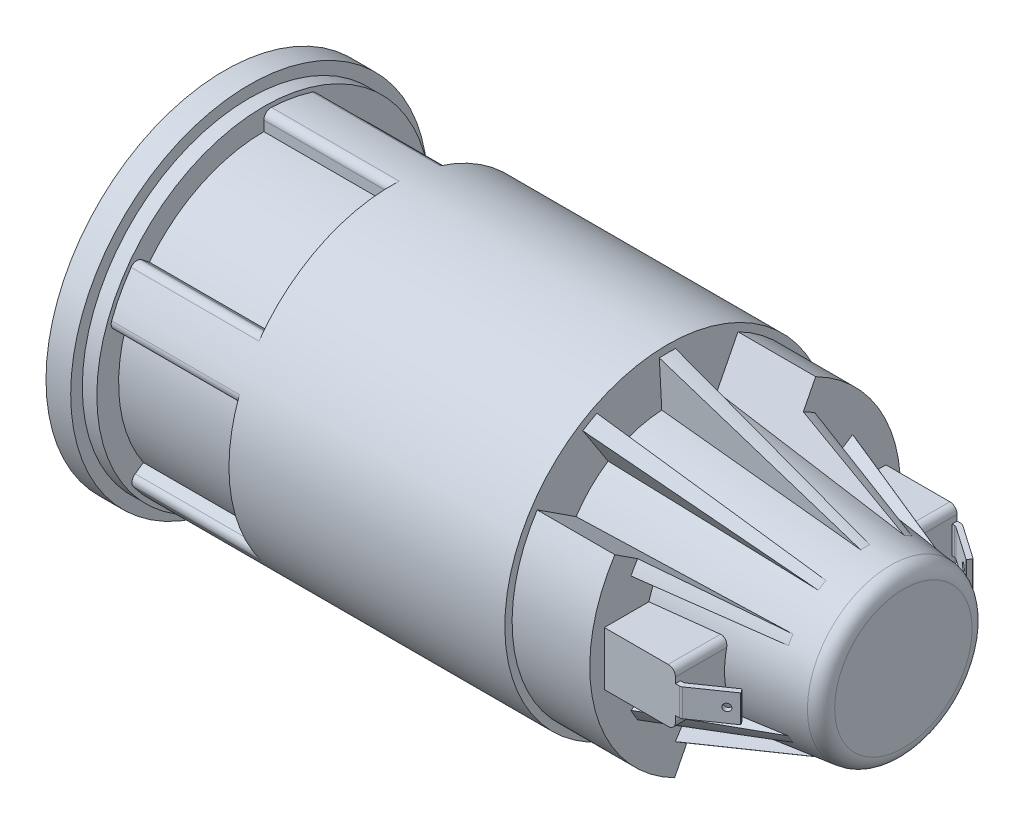
SolidWorks part; units mm, degrees
ref_plane "Front Plane" through (0, 0, 0) normal (0, 0, 1) x (1, 0, 0)
ref_plane "Top Plane" through (0, 0, 0) normal (0, 1, 0) x (1, 0, 0)
ref_plane "Right Plane" through (0, 0, 0) normal (1, 0, 0) x (0, 0, -1)
sketch "Sketch1" plane through (0, 0, 0) normal (1, 0, 0) x (0, 0, -1)
  circle A0 centre (0, 0) radius 7.493
  dimension "D1" = 14.986
extrude "Extrude1" add sketch "Sketch1" along normal blind 8.89
sketch "Sketch2" plane through (8.89, 0, 0) normal (1, 0, 0) x (0, 0, -1)
  circle A0 centre (0, 0) radius 31.242
  dimension "D1" = 62.484
extrude "Extrude2" add sketch "Sketch2" along normal blind 10.922
sketch "Sketch3" plane through (8.89, 0, 0) normal (-1, 0, 0) x (0, 0, 1)
  circle A0 centre (0, 0) radius 21.971
  circle A2 centre (0, 0) radius 7.493
  dimension "D1" = 43.942
extrude "Extrude3" cut sketch "Sketch3" against normal blind 5.969
sketch "Sketch4" plane through (8.89, 0, 0) normal (-1, 0, 0) x (0, 0, 1)
  circle A0 centre (0, 0) radius 23.8125
  circle A1 centre (0, 0) radius 31.242
  dimension "D1" = 47.625
extrude "Extrude4" cut sketch "Sketch4" against normal blind 4.064
sketch "Sketch5" plane through (14.859, 0, 0) normal (-1, 0, 0) x (0, 0, 1)
  circle A0 centre (0, 0) radius 9.144
  circle A1 centre (0, 0) radius 12.7
  dimension "D1" = 18.288
  dimension "D2" = 25.4
extrude "Extrude5" add sketch "Sketch5" along normal blind 3.048
sketch "Sketch6" plane through (19.812, 0, 0) normal (1, 0, 0) x (0, 0, -1)
  circle A0 centre (0, 0) radius 25.4
  dimension "D1" = 50.8
extrude "Extrude6" add sketch "Sketch6" along normal blind 22.352
sketch "Sketch7" plane through (19.812, 0, 0) normal (1, 0, 0) x (0, 0, -1)
  line L0 (0, 25.4) -> (0, 27.1483)
  line L1 (8.6873, 23.8682) -> (9.2853, 25.5111)
  circle A0 centre (0, 0) radius 31.242 construction
  arc A1 (8.47, 27.1578) -> (1.3293, 28.4169) centre (0, 0) ccw
  arc A2 (8.6873, 23.8682) -> (0, 25.4) centre (0, 0) ccw
  arc A3 (1.3293, 28.4169) -> (0, 27.1483) centre (1.27, 27.1483) ccw
  arc A4 (8.47, 27.1578) -> (9.2853, 25.5111) centre (8.0919, 25.9454) cw
  point P11 (0, 31.242)
  point P14 (10.6854, 29.3579)
  dimension "D2" = 1.27
  dimension "D1" = 56.896
extrude "Extrude7" add sketch "Sketch7" along normal up to surface (22.352 mm away) up to face at (42.164, 0, -25.4)
ref_axis "Axis1" through (-3.3782, 0, 0) along (1, 0, 0)
pattern_circular "CirPattern1" count 5 over 360 about axis through (-3.3782, 0, 0) along (1, 0, 0) of "Extrude7"
sketch "Sketch8" plane through (42.164, 0, 0) normal (1, 0, 0) x (0, 0, -1)
  circle A0 centre (0, 0) radius 28.448
  dimension "D1" = 56.896
extrude "Extrude8" add sketch "Sketch8" along normal blind 48.26
sketch "Sketch9" plane through (0, 0, 0) normal (0, 0, 1) x (1, 0, 0)
  line L0 (90.424, -28.448) -> (90.424, 28.448) construction
  line L1 (90.424, 0) -> (90.424, 19.05)
  line L2 (90.424, 0) -> (131.699, 0)
  line L3 (131.699, 0) -> (131.699, 12.0237)
  line L4 (129.4501, 14.547) -> (90.424, 19.05)
  arc A0 (129.4501, 14.547) -> (131.699, 12.0237) centre (129.159, 12.0237) cw
  point P9 (131.699, 14.2875)
  dimension "D4" = 2.54
  dimension "D1" = 14.2875
  dimension "D2" = 19.05
  dimension "D3" = 41.275
revolve "Revolve1" add sketch "Sketch9" angle 360 about axis through (-3.3782, 0, 0) along (1, 0, 0)
sketch "Sketch10" plane through (0, 0, 0) normal (0, 0, 1) x (1, 0, 0)
  line L0 (129.4501, 14.547) -> (90.424, 19.05) construction
  line L1 (125.0051, 15.0599) -> (90.424, 19.05)
  line L2 (90.424, -28.448) -> (90.424, 28.448) construction
  line L3 (90.424, 19.05) -> (90.424, 27.178)
  line L4 (125.0051, 15.0599) -> (90.424, 27.178)
  dimension "D1" = 4.445
  dimension "D2" = 1.27
revolve "Revolve2" add sketch "Sketch10" angle 6 mid plane about axis through (-3.3782, 0, 0) along (1, 0, 0)
pattern_circular "CirPattern2" count 12 over 360 of "Revolve2"
sketch "Sketch11" plane through (90.424, 0, 0) normal (1, 0, 0) x (0, 0, -1)
  line L0 (22.7934, -14.8022) -> (15.9767, -10.3754) construction
  line L1 (22.7934, -14.8022) -> (15.9767, -10.3754)
  line L2 (12.3386, 24.2158) -> (8.6485, 16.9737) construction
  line L3 (12.3386, 24.2158) -> (8.6485, 16.9737)
  line L4 (8.6485, 16.9737) -> (6.837, 13.4184)
  line L5 (15.9767, -10.3754) -> (12.6303, -8.2022)
  arc A0 (22.7934, -14.8022) -> (12.3386, 24.2158) centre (0, 0) ccw
  arc A1 (12.6303, -8.2022) -> (6.837, 13.4184) centre (0, 0) ccw
extrude "Extrude9" add sketch "Sketch11" along normal blind 13.589
pattern_circular "CirPattern3" count 2 over 360 about axis through (-3.3782, 0, 0) along (1, 0, 0) of "Extrude9"
sketch "Sketch12" plane through (104.013, 0, 0) normal (1, 0, 0) x (0, 0, -1)
  line L0 (0, 0) -> (27.178, 0) construction
  line L1 (0, -4.699) -> (24.638, -4.699)
  line L2 (0, 4.699) -> (24.638, 4.699)
  line L3 (24.638, 4.699) -> (24.638, -4.699)
  line L4 (0, 4.699) -> (27.178, 4.699) construction
  line L5 (0, -4.699) -> (27.178, -4.699) construction
  line L6 (0, 4.699) -> (0, -4.699)
  arc A0 (22.7934, -14.8022) -> (12.3386, 24.2158) centre (0, 0) ccw construction
  dimension "D3" = 24.638
  dimension "D1" = 4.699
  dimension "D2" = 4.699
extrude "Extrude10" add sketch "Sketch12" along normal blind 12.446
fillet "Fillet2" radius 1.27 2 edges at (116.459, 4.699, -19.9902) (116.459, -4.699, -19.9902)
pattern_circular "CirPattern4" count 2 over 360 about axis through (-3.3782, 0, 0) along (1, 0, 0) of "Extrude10", "Fillet2"
sketch "Sketch13" plane through (0, 0, 0) normal (0, 1, 0) x (1, 0, 0)
  line L0 (116.459, 24.638) -> (117.1294, 24.638)
  line L1 (117.564, 24.5019) -> (123.5415, 20.3513)
  line L2 (116.459, 23.749) -> (116.851, 23.749)
  line L3 (117.2856, 23.6129) -> (123.0139, 19.6354)
  line L4 (117.368, 24.638) -> (122.866, 20.8204) construction
  line L5 (117.0896, 23.749) -> (122.3589, 20.0902) construction
  line L6 (123.5591, 20.2432) -> (123.1185, 19.6524)
  line L7 (116.459, 24.638) -> (117.368, 24.638) construction
  line L8 (116.459, 23.749) -> (117.0896, 23.749) construction
  line L9 (116.459, 24.638) -> (116.459, 23.749)
  line L10 (90.424, 0) -> (129.4501, 0) construction
  line L11 (90.424, -1.4224) -> (90.424, 1.4224) construction
  line L12 (129.4501, -14.547) -> (129.4501, 14.547) construction
  line L13 (116.459, -24.638) -> (116.459, -23.749)
  line L14 (123.5591, -20.2432) -> (123.1185, -19.6524)
  line L15 (117.2856, -23.6129) -> (123.0139, -19.6354)
  line L16 (116.459, -23.749) -> (116.851, -23.749)
  line L17 (117.564, -24.5019) -> (123.5415, -20.3513)
  line L18 (116.459, -24.638) -> (117.1294, -24.638)
  arc A0 (117.564, 24.5019) -> (117.1294, 24.638) centre (117.1294, 23.876) ccw
  arc A1 (116.851, 23.749) -> (117.2856, 23.6129) centre (116.851, 22.987) cw
  arc A2 (123.5591, 20.2432) -> (123.5415, 20.3513) centre (123.498, 20.2888) ccw
  arc A3 (123.1185, 19.6524) -> (123.0139, 19.6354) centre (123.0574, 19.698) cw
  arc A4 (123.1185, -19.6524) -> (123.0139, -19.6354) centre (123.0574, -19.698) ccw
  arc A5 (123.5591, -20.2432) -> (123.5415, -20.3513) centre (123.498, -20.2888) cw
  arc A6 (116.851, -23.749) -> (117.2856, -23.6129) centre (116.851, -22.987) ccw
  arc A7 (117.564, -24.5019) -> (117.1294, -24.638) centre (117.1294, -23.876) cw
  dimension "D2" = 0.762
  dimension "D3" = 0.762
  dimension "D4" = 0.0762
  dimension "D1" = 0.889
extrude "Extrude11" add sketch "Sketch13" along normal blind 2.413 and the other way blind 2.413
sketch "Sketch14" plane through (0, 0, 0) normal (-1, 0, 0) x (0, 0, 1)
  line L0 (-0.1536, 6.3053) -> (-0.7728, 7.1492)
  line L1 (0, 0) -> (0, 9.6788) construction
  line L2 (0.1536, 6.3053) -> (0.7728, 7.1492)
  line L3 (1.7803, 6.0507) -> (2.5968, 6.7056)
  line L4 (1.4836, 6.1302) -> (1.1039, 7.1056)
  line L5 (3.2857, 5.3838) -> (4.2438, 5.805)
  line L6 (3.0196, 5.5374) -> (2.9053, 6.5778)
  line L7 (4.5671, 4.3499) -> (5.6017, 4.5088)
  line L8 (4.3499, 4.5671) -> (4.5088, 5.6017)
  line L9 (5.5374, 3.0196) -> (6.5778, 2.9053)
  line L10 (5.3838, 3.2857) -> (5.805, 4.2438)
  line L11 (6.1302, 1.4836) -> (7.1056, 1.1039)
  line L12 (6.0507, 1.7803) -> (6.7056, 2.5968)
  line L13 (6.3053, -0.1536) -> (7.1492, -0.7728)
  line L14 (6.3053, 0.1536) -> (7.1492, 0.7728)
  line L15 (6.0507, -1.7803) -> (6.7056, -2.5968)
  line L16 (6.1302, -1.4836) -> (7.1056, -1.1039)
  line L17 (5.3838, -3.2857) -> (5.805, -4.2438)
  line L18 (5.5374, -3.0196) -> (6.5778, -2.9053)
  line L19 (4.3499, -4.5671) -> (4.5088, -5.6017)
  line L20 (4.5671, -4.3499) -> (5.6017, -4.5088)
  line L21 (3.0196, -5.5374) -> (2.9053, -6.5778)
  line L22 (3.2857, -5.3838) -> (4.2438, -5.805)
  line L23 (1.4836, -6.1302) -> (1.1039, -7.1056)
  line L24 (1.7803, -6.0507) -> (2.5968, -6.7056)
  line L25 (-0.1536, -6.3053) -> (-0.7728, -7.1492)
  line L26 (0.1536, -6.3053) -> (0.7728, -7.1492)
  line L27 (-1.7803, -6.0507) -> (-2.5968, -6.7056)
  line L28 (-1.4836, -6.1302) -> (-1.1039, -7.1056)
  line L29 (-3.2857, -5.3838) -> (-4.2438, -5.805)
  line L30 (-3.0196, -5.5374) -> (-2.9053, -6.5778)
  line L31 (-4.5671, -4.3499) -> (-5.6017, -4.5088)
  line L32 (-4.3499, -4.5671) -> (-4.5088, -5.6017)
  line L33 (-5.5374, -3.0196) -> (-6.5778, -2.9053)
  line L34 (-5.3838, -3.2857) -> (-5.805, -4.2438)
  line L35 (-6.1302, -1.4836) -> (-7.1056, -1.1039)
  line L36 (-6.0507, -1.7803) -> (-6.7056, -2.5968)
  line L37 (-6.3053, 0.1536) -> (-7.1492, 0.7728)
  line L38 (-6.3053, -0.1536) -> (-7.1492, -0.7728)
  line L39 (-6.0507, 1.7803) -> (-6.7056, 2.5968)
  line L40 (-6.1302, 1.4836) -> (-7.1056, 1.1039)
  line L41 (-5.3838, 3.2857) -> (-5.805, 4.2438)
  line L42 (-5.5374, 3.0196) -> (-6.5778, 2.9053)
  line L43 (-4.3499, 4.5671) -> (-4.5088, 5.6017)
  line L44 (-4.5671, 4.3499) -> (-5.6017, 4.5088)
  line L45 (-3.0196, 5.5374) -> (-2.9053, 6.5778)
  line L46 (-3.2857, 5.3838) -> (-4.2438, 5.805)
  line L47 (-1.4836, 6.1302) -> (-1.1039, 7.1056)
  line L48 (-1.7803, 6.0507) -> (-2.5968, 6.7056)
  circle A0 centre (0, 0) radius 6.096 construction
  arc A1 (-3.2857, 5.3838) -> (-3.0196, 5.5374) centre (-3.209, 5.5582) ccw
  arc A2 (-2.9053, 6.5778) -> (-2.5968, 6.7056) centre (-2.716, 6.557) cw
  arc A3 (-1.4836, 6.1302) -> (-1.7803, 6.0507) centre (-1.6611, 6.1993) cw
  arc A4 (-0.7728, 7.1492) -> (-1.1039, 7.1056) centre (-0.9264, 7.0365) ccw
  arc A5 (0.1536, 6.3053) -> (-0.1536, 6.3053) centre (0, 6.418) cw
  arc A6 (1.1039, 7.1056) -> (0.7728, 7.1492) centre (0.9264, 7.0365) ccw
  arc A7 (1.7803, 6.0507) -> (1.4836, 6.1302) centre (1.6611, 6.1993) cw
  arc A8 (2.9053, 6.5778) -> (2.5968, 6.7056) centre (2.716, 6.557) ccw
  arc A9 (3.2857, 5.3838) -> (3.0196, 5.5374) centre (3.209, 5.5582) cw
  arc A10 (4.5088, 5.6017) -> (4.2438, 5.805) centre (4.3205, 5.6306) ccw
  arc A11 (4.5671, 4.3499) -> (4.3499, 4.5671) centre (4.5382, 4.5382) cw
  arc A12 (5.805, 4.2438) -> (5.6017, 4.5088) centre (5.6306, 4.3205) ccw
  arc A13 (5.5374, 3.0196) -> (5.3838, 3.2857) centre (5.5582, 3.209) cw
  arc A14 (6.7056, 2.5968) -> (6.5778, 2.9053) centre (6.557, 2.716) ccw
  arc A15 (6.1302, 1.4836) -> (6.0507, 1.7803) centre (6.1993, 1.6611) cw
  arc A16 (7.1492, 0.7728) -> (7.1056, 1.1039) centre (7.0365, 0.9264) ccw
  arc A17 (6.3053, -0.1536) -> (6.3053, 0.1536) centre (6.418, 0) cw
  arc A18 (7.1056, -1.1039) -> (7.1492, -0.7728) centre (7.0365, -0.9264) ccw
  arc A19 (6.0507, -1.7803) -> (6.1302, -1.4836) centre (6.1993, -1.6611) cw
  arc A20 (6.5778, -2.9053) -> (6.7056, -2.5968) centre (6.557, -2.716) ccw
  arc A21 (5.3838, -3.2857) -> (5.5374, -3.0196) centre (5.5582, -3.209) cw
  arc A22 (5.6017, -4.5088) -> (5.805, -4.2438) centre (5.6306, -4.3205) ccw
  arc A23 (4.3499, -4.5671) -> (4.5671, -4.3499) centre (4.5382, -4.5382) cw
  arc A24 (4.2438, -5.805) -> (4.5088, -5.6017) centre (4.3205, -5.6306) ccw
  arc A25 (3.0196, -5.5374) -> (3.2857, -5.3838) centre (3.209, -5.5582) cw
  arc A26 (2.5968, -6.7056) -> (2.9053, -6.5778) centre (2.716, -6.557) ccw
  arc A27 (1.4836, -6.1302) -> (1.7803, -6.0507) centre (1.6611, -6.1993) cw
  arc A28 (0.7728, -7.1492) -> (1.1039, -7.1056) centre (0.9264, -7.0365) ccw
  arc A29 (0.1536, -6.3053) -> (-0.1536, -6.3053) centre (0, -6.418) ccw
  arc A30 (-0.7728, -7.1492) -> (-1.1039, -7.1056) centre (-0.9264, -7.0365) cw
  arc A31 (-1.7803, -6.0507) -> (-1.4836, -6.1302) centre (-1.6611, -6.1993) cw
  arc A32 (-2.9053, -6.5778) -> (-2.5968, -6.7056) centre (-2.716, -6.557) ccw
  arc A33 (-3.2857, -5.3838) -> (-3.0196, -5.5374) centre (-3.209, -5.5582) cw
  arc A34 (-4.5088, -5.6017) -> (-4.2438, -5.805) centre (-4.3205, -5.6306) ccw
  arc A35 (-4.5671, -4.3499) -> (-4.3499, -4.5671) centre (-4.5382, -4.5382) cw
  arc A36 (-5.6017, -4.5088) -> (-5.805, -4.2438) centre (-5.6306, -4.3205) cw
  arc A37 (-5.5374, -3.0196) -> (-5.3838, -3.2857) centre (-5.5582, -3.209) cw
  arc A38 (-6.7056, -2.5968) -> (-6.5778, -2.9053) centre (-6.557, -2.716) ccw
  arc A39 (-6.1302, -1.4836) -> (-6.0507, -1.7803) centre (-6.1993, -1.6611) cw
  arc A40 (-7.1492, -0.7728) -> (-7.1056, -1.1039) centre (-7.0365, -0.9264) ccw
  arc A41 (-6.3053, 0.1536) -> (-6.3053, -0.1536) centre (-6.418, 0) cw
  arc A42 (-7.1056, 1.1039) -> (-7.1492, 0.7728) centre (-7.0365, 0.9264) ccw
  arc A43 (-6.0507, 1.7803) -> (-6.1302, 1.4836) centre (-6.1993, 1.6611) cw
  arc A44 (-6.5778, 2.9053) -> (-6.7056, 2.5968) centre (-6.557, 2.716) ccw
  arc A45 (-5.3838, 3.2857) -> (-5.5374, 3.0196) centre (-5.5582, 3.209) cw
  arc A46 (-5.6017, 4.5088) -> (-5.805, 4.2438) centre (-5.6306, 4.3205) ccw
  arc A47 (-4.3499, 4.5671) -> (-4.5671, 4.3499) centre (-4.5382, 4.5382) cw
  arc A48 (-4.2438, 5.805) -> (-4.5088, 5.6017) centre (-4.3205, 5.6306) ccw
  circle A49 centre (0, 0) radius 7.493
  point P33 (-0.978, 7.4289)
  point P42 (0, 6.096)
  point P51 (0.978, 7.4289)
  dimension "D1" = 12.192
  dimension "D3" = 0.1905
  dimension "D2" = 15
extrude "Extrude12" cut sketch "Sketch14" against normal up to surface (14.859 mm away) up to face at (14.859, 0, 9.144)
sketch "Sketch16" plane through (0, 0, 0) normal (-1, 0, 0) x (0, 0, 1)
  circle A0 centre (0, 0) radius 2.794
  dimension "D1" = 5.588
extrude "Extrude14" add sketch "Sketch16" along normal blind 1.016
sketch "Sketch17" plane through (49.7222, 0, -71.6086) normal (0.5703, 0, -0.8214) x (-0.8214, 0, -0.5703)
  line L0 (-82.5927, 0) -> (-89.8699, 0) construction
  line L1 (-82.5927, -2.413) -> (-82.5927, 2.413) construction
  line L2 (-89.8699, -2.413) -> (-89.8699, 2.413) construction
  line L3 (-89.9461, 2.413) -> (-89.9461, -2.413) construction
  circle A0 centre (-88.0411, 0) radius 0.635
  dimension "D1" = 1.27
  dimension "D2" = 1.905
extrude "Extrude16" cut sketch "Sketch17" against normal blind 2.54
sketch "Sketch18" plane through (49.7222, 0, 71.6086) normal (0.5703, 0, 0.8214) x (0.8214, 0, -0.5703)
  line L0 (82.5927, 0) -> (89.8699, 0) construction
  line L1 (82.5927, -2.413) -> (82.5927, 2.413) construction
  line L2 (89.8699, -2.413) -> (89.8699, 2.413) construction
  line L3 (89.9461, -2.413) -> (89.9461, 2.413) construction
  circle A0 centre (88.1681, 0) radius 0.635
  dimension "D1" = 1.27
  dimension "D2" = 1.778
extrude "Extrude17" cut sketch "Sketch18" against normal blind 2.54
sketch "Sketch19" plane through (19.812, 0, 0) normal (1, 0, 0) x (0, 0, -1)
  circle A0 centre (0, 0) radius 29.21
  circle A1 centre (0, 0) radius 31.242
  dimension "D1" = 58.42
extrude "Extrude18" cut sketch "Sketch19" against normal blind 2.54
sketch "Sketch20" plane through (12.954, 0, 0) normal (-1, 0, 0) x (0, 0, 1)
  circle A0 centre (0, 0) radius 29.1706
  circle A1 centre (0, 0) radius 23.8125
extrude "Extrude19" cut sketch "Sketch20" against normal blind 2.54
sketch "Sketch21" plane through (8.89, 0, 0) normal (-1, 0, 0) x (0, 0, 1)
  circle A0 centre (0, 0) radius 45.008
  circle A1 centre (0, 0) radius 9.144 construction
  circle A2 centre (0, 0) radius 9.144
extrude "Extrude20" cut sketch "Sketch21" against normal up to surface (2.921 mm away) up to face at (11.811, 0, 12.7)
